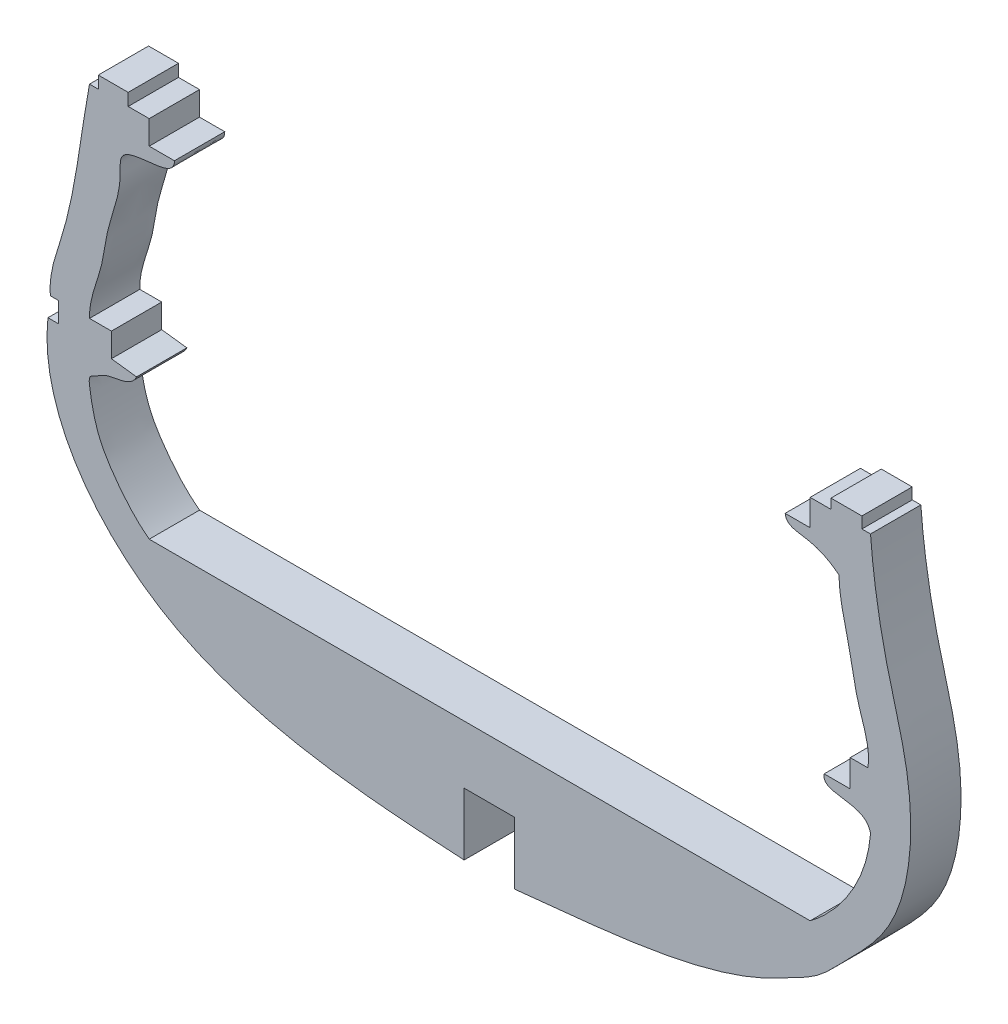
SolidWorks part; units mm, degrees
ref_plane "前视基准面" through (0, 0, 0) normal (0, 0, 1) x (1, 0, 0)
ref_plane "上视基准面" through (0, 0, 0) normal (0, 1, 0) x (1, 0, 0)
ref_plane "右视基准面" through (0, 0, 0) normal (1, 0, 0) x (0, 0, -1)
other "Configuration Table"
sketch "草图1" plane through (0, 0, 0) normal (0, 0, 1) x (1, 0, 0)
  line L0 (376.5, 617) -> (1882.5, 617) construction
  line L66 (466.6104, 742.2175) -> (571.6905, 742.2175)
  line L67 (573.9188, 763.5599) -> (578.0612, 763.5599)
  line L68 (578.0612, 763.5599) -> (578.0612, 767.8686)
  line L69 (578.0612, 767.8686) -> (580.8571, 767.8686)
  line L70 (567.7144, 796.3297) -> (571.6905, 796.3297)
  line L71 (571.6905, 796.3297) -> (571.6905, 800.5194)
  line L72 (571.6905, 800.5194) -> (575.0009, 800.5194)
  line L73 (575.0009, 800.5194) -> (575.0009, 802.0713)
  line L74 (575.0009, 802.0713) -> (579.9195, 802.0713)
  line L75 (579.9195, 802.0713) -> (579.9195, 800.2774)
  line L76 (579.9195, 800.2774) -> (581.2908, 800.2774)
  line L77 (516.681, 723.0752) -> (516.681, 732.2341)
  line L79 (524.682, 732.2341) -> (524.682, 723.0752)
  line L80 (450.9003, 767.8686) -> (452.1686, 767.8686)
  line L81 (452.1686, 767.8686) -> (452.1686, 764.663)
  line L82 (452.1686, 764.663) -> (450.5102, 764.663)
  line L83 (457.1149, 800.1249) -> (458.51, 800.1249)
  line L84 (458.51, 800.1249) -> (458.51, 802.0713)
  line L85 (458.51, 802.0713) -> (463.2661, 802.0713)
  line L86 (463.2661, 802.0713) -> (463.2661, 800.1249)
  line L87 (463.2661, 800.1249) -> (466.6104, 800.1249)
  line L88 (466.6104, 800.1249) -> (466.6104, 796.3297)
  line L89 (466.6104, 796.3297) -> (470.6221, 796.3297)
  line L90 (457.1149, 767.8686) -> (460.6027, 767.8686)
  line L91 (460.6027, 767.8686) -> (460.6027, 764.0611)
  line L92 (460.6027, 764.0611) -> (464.5978, 763.5599)
  line L93 (516.681, 732.9752) -> (524.682, 732.9752)
  line L94 (516.681, 732.2341) -> (516.681, 732.9752)
  line L95 (524.682, 732.9752) -> (524.682, 732.2341)
  spline S25 degree 3 poles (571.6905, 742.2175) (576.9656, 746.1846) (580.7953, 752.3798) (581.2908, 759.0325) knots 0 0 0 0 1 1 1 1
  spline S26 degree 3 poles (581.2908, 759.0325) (580.7983, 761.218) (577.3856, 761.4809) (573.6861, 762.2327) (573.9188, 763.5599) knots 0 0 0 0 0.647424 1 1 1 1
  spline S27 degree 3 poles (580.8571, 767.8686) (581.36, 770.8472) (579.1415, 775.3935) (577.975, 783.5776) (576.3296, 788.706) (576.2592, 792.1471) knots 0 0 0 0 0.352753 0.588696 1 1 1 1
  spline S28 degree 3 poles (567.7144, 796.3297) (567.8825, 794.862) (571.9634, 794.6694) (574.4938, 793.5166) (576.2592, 792.1471) knots 0 0 0 0 0.387326 1 1 1 1
  spline S29 degree 3 poles (581.2908, 800.2774) (581.7526, 794.1551) (583.333, 784.6708) (587.3584, 771.289) (588.2242, 759.3034) (584.9565, 746.8239) (577.9419, 740.2708) (572.9107, 734.9486) (568.5963, 732.8569) (562.8064, 729.7553) (548.5465, 725.0696) (534.8851, 724.1889) (524.682, 723.0752) knots 0 0 0 0 0.152615 0.23818 0.346667 0.448689 0.545213 0.580365 0.629911 0.662614 0.743993 1 1 1 1
  spline S30 degree 3 poles (516.681, 723.0752) (506.3247, 723.6539) (489.6705, 724.717) (462.0601, 734.2959) (449.0889, 751.8017) (450.5102, 764.663) knots 0 0 0 0 0.358877 0.569205 1 1 1 1
  spline S31 degree 3 poles (450.9003, 767.8686) (450.6186, 771.0528) (454.751, 781.3064) (455.6632, 792.4057) (457.1149, 800.1249) knots 0 0 0 0 0.27932 1 1 1 1
  spline S32 degree 3 poles (457.1149, 767.8686) (457.0464, 770.8507) (459.0576, 774.7684) (459.6411, 780.1126) (460.8888, 784.6844) (462.258, 788.4972) (461.5628, 795.5066) (470.707, 793.1025) (470.6221, 796.3297) knots 0 0 0 0 0.254341 0.369748 0.466004 0.663215 0.735185 1 1 1 1
  spline S33 degree 3 poles (466.6104, 742.2175) (464.277, 743.9291) (459.7934, 749.507) (457.8709, 753.4707) (456.8447, 760.2387) (457.706, 760.1166) (458.9062, 760.9012) knots 0 0 0 0 0.369244 0.820134 0.903852 1 1 1 1
  spline S34 degree 3 poles (458.9062, 760.9012) (460.6234, 762.075) (463.5514, 761.2859) (464.5978, 763.5599) knots 0 0 0 0 1 1 1 1
  dimension "D1" = 8.001
  dimension "D3" = 9.9
extrude "凸台-拉伸1" add sketch "草图1" along normal blind 8
